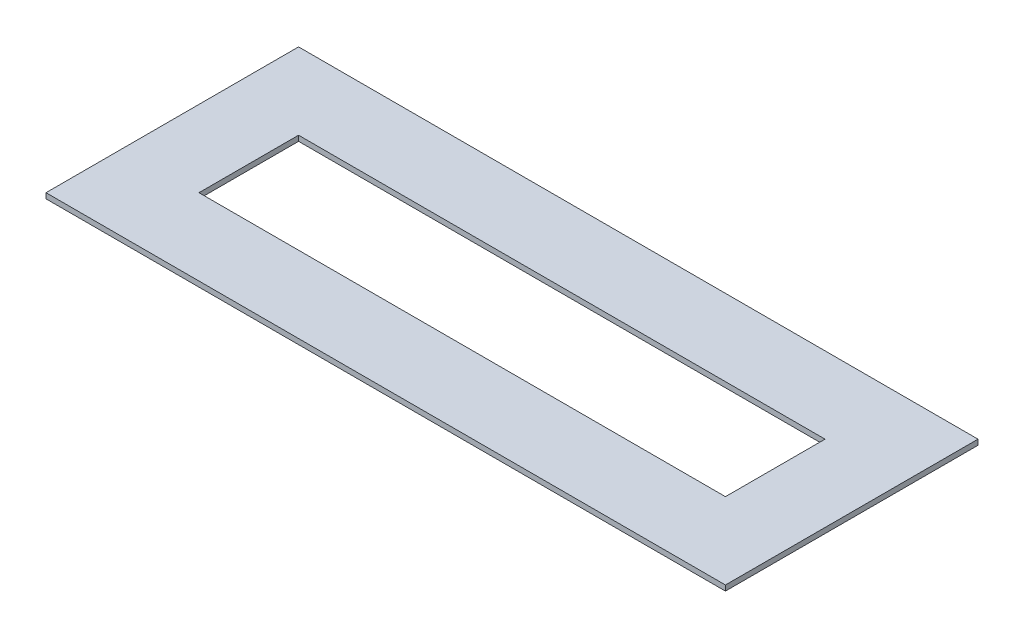
SolidWorks part; units mm, degrees
material "Maple"
ref_plane "Front Plane" through (0, 0, 0) normal (0, 0, 1) x (1, 0, 0)
ref_plane "Top Plane" through (0, 0, 0) normal (0, 1, 0) x (1, 0, 0)
ref_plane "Right Plane" through (0, 0, 0) normal (1, 0, 0) x (0, 0, -1)
sketch "Sketch1" plane through (0, 0, 0) normal (0, 1, 0) x (1, 0, 0)
  line L1 (-303.2125, -112.7125) -> (303.2125, -112.7125)
  line L2 (-303.2125, -112.7125) -> (-303.2125, 112.7125)
  line L3 (-303.2125, 112.7125) -> (303.2125, 112.7125)
  line L4 (303.2125, -112.7125) -> (303.2125, 112.7125)
  line L5 (-303.2125, -112.7125) -> (303.2125, 112.7125) construction
  line L6 (-303.2125, 112.7125) -> (303.2125, -112.7125) construction
  point P0 (0, 0)
  dimension "D1" = 225.425
  dimension "D2" = 606.425
extrude "Boss-Extrude1" add sketch "Sketch1" along normal mid plane 4.7625 contours L3 L4 L1 L2
sketch "Sketch2" [suppressed] plane through (0, 2.3813, 0) normal (0, 1, 0) x (1, 0, 0)
  line L0 (-279.4, -152.4) -> (-279.4, 152.4) construction
  line L1 (-279.4, 133.35) -> (-247.65, 133.35)
  line L2 (-279.4, 133.35) -> (-279.4, -133.35)
  line L3 (-279.4, -133.35) -> (-247.65, -133.35)
  line L4 (-247.65, 133.35) -> (-247.65, -133.35)
  line L5 (279.4, -152.4) -> (279.4, 152.4) construction
  line L6 (279.4, 133.35) -> (247.65, 133.35)
  line L7 (279.4, 133.35) -> (279.4, -133.35)
  line L8 (279.4, -133.35) -> (247.65, -133.35)
  line L9 (247.65, 133.35) -> (247.65, -133.35)
  line L10 (-247.65, 0) -> (247.65, 0) construction
  line L11 (-279.4, -152.4) -> (279.4, -152.4) construction
  dimension "D1" = 38.1
  dimension "D2" = 19.05
extrude "Cut-Extrude1" [suppressed] cut sketch "Sketch2" against normal through all
sketch "Sketch3" [suppressed] plane through (0, 2.3813, 0) normal (0, 1, 0) x (1, 0, 0)
  line L0 (-279.4, 152.4) -> (279.4, 152.4) construction
  line L1 (-196.85, 152.4) -> (196.85, 152.4)
  line L2 (-196.85, 152.4) -> (-196.85, 127)
  line L3 (-196.85, 127) -> (196.85, 127)
  line L4 (196.85, 152.4) -> (196.85, 127)
  line L5 (0, 0) -> (0, 127) construction
  line L6 (-247.65, -133.35) -> (-247.65, 133.35) construction
  dimension "D1" = 50.8
  dimension "D2" = 25.4
extrude "Cut-Extrude2" [suppressed] cut sketch "Sketch3" against normal through all
sketch "Sketch4" [suppressed] plane through (0, 2.3813, 0) normal (0, 1, 0) x (1, 0, 0)
  line L0 (-200.025, 123.825) -> (200.025, 123.825) construction
  line L1 (-200.025, 133.35) -> (200.025, 133.35)
  line L2 (-200.025, 114.3) -> (200.025, 114.3)
  line L3 (-279.4, -152.4) -> (279.4, -152.4) construction
  line L4 (-279.4, 152.4) -> (-234.95, 152.4)
  line L5 (-279.4, 152.4) -> (-279.4, -152.4)
  line L7 (0, 123.825) -> (0, 0) construction
  line L8 (-279.4, 152.4) -> (279.4, 152.4) construction
  line L9 (-279.4, -152.4) -> (-234.95, -152.4)
  line L10 (-234.95, 152.4) -> (-234.95, -152.4)
  line L12 (279.4, 152.4) -> (234.95, 152.4)
  line L13 (279.4, 152.4) -> (279.4, -152.4)
  line L14 (279.4, -152.4) -> (234.95, -152.4)
  line L15 (234.95, 152.4) -> (234.95, -152.4)
  arc A0 (-200.025, 133.35) -> (-200.025, 114.3) centre (-200.025, 123.825) ccw
  arc A1 (200.025, 114.3) -> (200.025, 133.35) centre (200.025, 123.825) ccw
  point P2 (0, 123.825)
  dimension "D1" = 25.4
  dimension "D2" = 19.05
  dimension "D3" = 19.05
  dimension "D4" = 44.45
extrude "Cut-Extrude3" [suppressed] cut sketch "Sketch4" against normal through all
sketch "Sketch5" [suppressed] plane through (0, 2.3813, 0) normal (0, 1, 0) x (1, 0, 0)
  line L0 (-234.95, 152.4) -> (-234.95, -152.4)
  line L1 (-279.4, 152.4) -> (279.4, 152.4) construction
  line L2 (-279.4, -152.4) -> (279.4, -152.4) construction
  line L3 (-279.4, -152.4) -> (-279.4, -133.35) construction
  dimension "D1" = 44.45
extrude "Cut-Extrude4" [suppressed] cut sketch "Sketch5" against normal through all and the other way through all
sketch "Sketch6" [suppressed] plane through (0, 2.3813, 0) normal (0, 1, 0) x (1, 0, 0)
  line L0 (-200.025, 123.825) -> (200.025, 123.825) construction
  line L1 (-200.025, 133.35) -> (200.025, 133.35)
  line L2 (-200.025, 114.3) -> (200.025, 114.3)
  line L3 (-298.45, 152.4) -> (298.45, 152.4) construction
  line L4 (298.45, -152.4) -> (298.45, 152.4) construction
  arc A0 (-200.025, 133.35) -> (-200.025, 114.3) centre (-200.025, 123.825) ccw
  arc A1 (200.025, 114.3) -> (200.025, 133.35) centre (200.025, 123.825) ccw
  point P2 (0, 123.825)
  dimension "D1" = 19.05
  dimension "D2" = 19.05
  dimension "D3" = 88.9
extrude "Cut-Extrude5" [suppressed] cut sketch "Sketch6" against normal through all
sketch "Sketch7" plane through (0, 2.3813, 0) normal (0, 1, 0) x (1, 0, 0)
  line L1 (-234.95, -44.45) -> (234.95, -44.45)
  line L2 (-234.95, -44.45) -> (-234.95, 44.45)
  line L3 (-234.95, 44.45) -> (234.95, 44.45)
  line L4 (234.95, -44.45) -> (234.95, 44.45)
  line L5 (-234.95, -44.45) -> (234.95, 44.45) construction
  line L6 (-234.95, 44.45) -> (234.95, -44.45) construction
  point P0 (0, 0)
  dimension "D1" = 88.9
  dimension "D2" = 469.9
extrude "Cut-Extrude6" cut sketch "Sketch7" against normal through all
sketch "Sketch8" [suppressed] plane through (0, 2.3813, 0) normal (0, 1, 0) x (1, 0, 0)
  line L0 (-15.875, 123.825) -> (15.875, 123.825) construction
  line L1 (-15.875, 133.35) -> (15.875, 133.35)
  line L2 (-15.875, 114.3) -> (15.875, 114.3)
  line L3 (0, 123.825) -> (0, 0) construction
  line L4 (-298.45, 152.4) -> (298.45, 152.4) construction
  arc A0 (-15.875, 133.35) -> (-15.875, 114.3) centre (-15.875, 123.825) ccw
  arc A1 (15.875, 114.3) -> (15.875, 133.35) centre (15.875, 123.825) ccw
  point P2 (0, 123.825)
  dimension "D2" = 50.8
  dimension "D1" = 19.05
  dimension "D3" = 19.05
extrude "Cut-Extrude7" [suppressed] cut sketch "Sketch8" against normal through all
